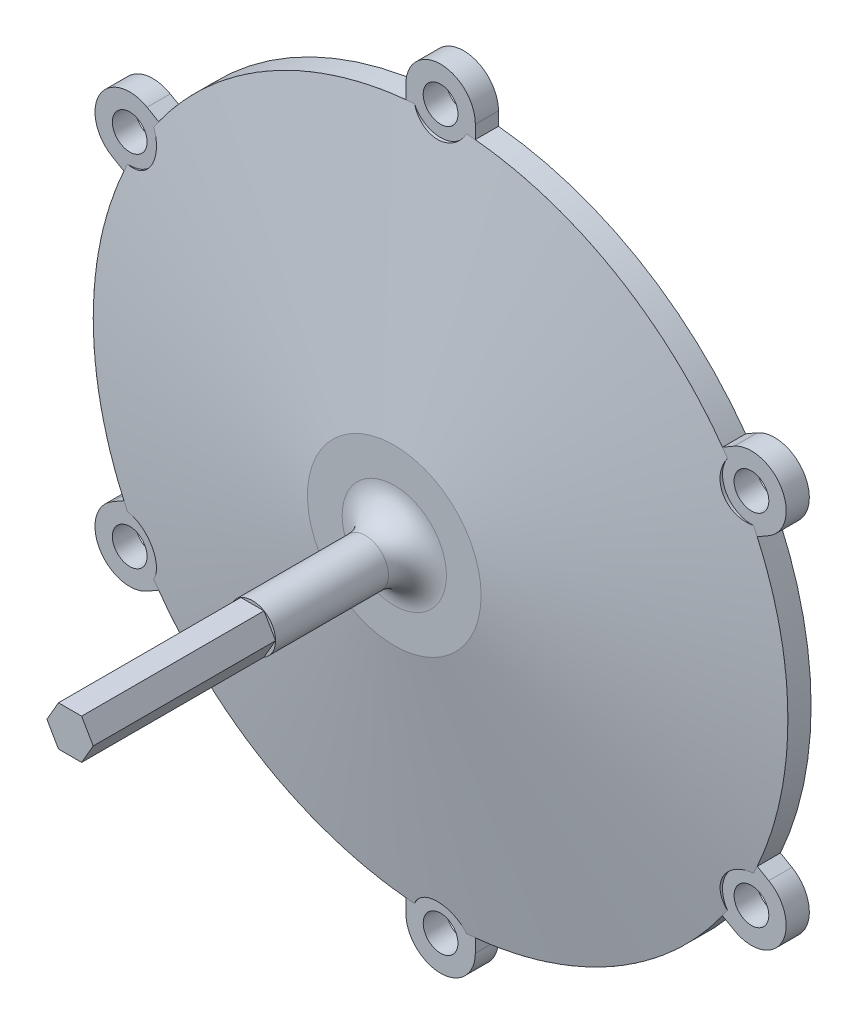
SolidWorks part; units mm, degrees
other "Markup1"
sketch "Sketch15" plane through (-60, 68, 48) normal (-0.9801, 0.1341, 0.1467) x (0.1373, -0.0767, 0.9876)
material "PETG"
ref_plane "Front Plane" through (0, 0, 0) normal (0, 0, 1) x (1, 0, 0)
ref_plane "Top Plane" through (0, 0, 0) normal (0, 1, 0) x (1, 0, 0)
ref_plane "Right Plane" through (0, 0, 0) normal (1, 0, 0) x (0, 0, -1)
sketch "Sketch1" plane through (0, 0, 0) normal (0, 0, 1) x (1, 0, 0)
  line L0 (-6, 62) -> (-6, 59.6992)
  line L1 (6, 62) -> (6, 59.6992)
  line L2 (50.6936, 36.1962) -> (48.7011, 35.0458)
  line L3 (56.6936, 25.8038) -> (54.7011, 24.6535)
  line L4 (56.6936, -25.8038) -> (54.7011, -24.6535)
  line L5 (50.6936, -36.1962) -> (48.7011, -35.0458)
  line L6 (6, -62) -> (6, -59.6992)
  line L7 (-6, -62) -> (-6, -59.6992)
  line L8 (-50.6936, -36.1962) -> (-48.7011, -35.0458)
  line L9 (-56.6936, -25.8038) -> (-54.7011, -24.6535)
  line L10 (-56.6936, 25.8038) -> (-54.7011, 24.6535)
  line L11 (-50.6936, 36.1962) -> (-48.7011, 35.0458)
  line L12 (0, 0) -> (6, 59.6992) construction
  circle A0 centre (0, 0) radius 57
  circle A1 centre (0, 0) radius 60
  arc A2 (6, 62) -> (-6, 62) centre (0, 62) ccw
  arc A3 (56.6936, 25.8038) -> (50.6936, 36.1962) centre (53.6936, 31) ccw
  arc A4 (50.6936, -36.1962) -> (56.6936, -25.8038) centre (53.6936, -31) ccw
  arc A5 (-6, -62) -> (6, -62) centre (0, -62) ccw
  arc A6 (-56.6936, -25.8038) -> (-50.6936, -36.1962) centre (-53.6936, -31) ccw
  arc A7 (-50.6936, 36.1962) -> (-56.6936, 25.8038) centre (-53.6936, 31) ccw
  dimension "D1" = 120
  dimension "D2" = 3
  dimension "D3" = 6
  dimension "D4" = 62
  dimension "D5" = 6
extrude "Boss-Extrude1" add sketch "Sketch1" along normal blind 4 contours L11 A7 L10 A1 | L1 A2 L0 A1 | L3 A3 L2 A1 | L5 A4 L4 A1 | L7 A5 L6 A1 | L9 A6 L8 A1 | A0 A1 region at (0, 63.4372, 0) region at (0, 58.3029, 0) region at (-54.9382, 31.7186, 0) region at (54.9382, 31.7186, 0) region at (-54.9382, -31.7186, 0) region at (54.9382, -31.7186, 0) region at (0, -63.4372, 0)
sketch "Sketch3" plane through (0, 0, 0) normal (0, 1, 0) x (1, 0, 0)
  line L0 (0, -4) -> (60, -4)
  line L1 (-6, -4) -> (6, -4) construction
  line L2 (60, -4) -> (15, -12)
  line L3 (15, -12) -> (0, -12)
  line L4 (0, -12) -> (0, -4)
  line L5 (48.7011, 0) -> (6, 0) construction
  line L6 (48.7011, 0) -> (6, 0) construction
  line L7 (0, -4) -> (60, -4)
  line L8 (0, -4) -> (0, -0.5)
  line L9 (0, -0.5) -> (57, -0.5)
  line L13 (57, -0.5) -> (57, -4)
  line L15 (-57, -4) -> (57, -4) construction
  dimension "D1" = 12
  dimension "D2" = 15
  dimension "D3" = 0.5
  dimension "D4" = 3
revolve "Revolve1" add sketch "Sketch3" angle 360 about L4 region at (28.5, 0, 2.25) region at (21, 0, 7.2)
sketch "Sketch4" plane through (0, 0, 0.5) normal (0, 0, 1) x (1, 0, 0)
  circle A0 centre (0, 0) radius 14
  dimension "D1" = 28
extrude "Cut-Extrude1" cut sketch "Sketch4" along normal blind 7 contours A0
sketch "Sketch9" plane through (0, 0, 7.5) normal (0, 0, -1) x (-1, 0, 0)
  circle A0 centre (0, 0) radius 11.5
  dimension "D1" = 23
extrude "Cut-Extrude4" cut sketch "Sketch9" against normal blind 0.5
sketch "Sketch10" plane through (0, 0, 12) normal (0, 0, 1) x (1, 0, 0)
  circle A0 centre (0, 0) radius 4
  dimension "D1" = 8
extrude "Boss-Extrude2" add sketch "Sketch10" along normal blind 56
fillet "Fillet1" radius 5 1 edges at (4, 0, 12)
sketch "Sketch7" plane through (0, 0, 4) normal (0, 0, 1) x (1, 0, 0)
  circle A0 centre (0, 62) radius 3
  arc A1 (6, 62) -> (-6, 62) centre (0, 62) ccw construction
  dimension "D1" = 6
extrude "Cut-Extrude2" cut sketch "Sketch7" against normal through all
sketch "Sketch8" plane through (0, 0, 4) normal (0, 0, 1) x (1, 0, 0)
  circle A0 centre (0, 62) radius 5
  dimension "D1" = 10
extrude "Cut-Extrude3" cut sketch "Sketch8" along normal through all
pattern_circular "CirPattern6" count 6 over 360 about axis through (0, 0, 4) along (0, 0, 1) of "Cut-Extrude2", "Cut-Extrude3"
sketch "Sketch11" plane through (0, 0, 68) normal (0, 0, 1) x (1, 0, 0)
  line L5 (2, 3.4641) -> (-2, 3.4641)
  line L6 (-2, 3.4641) -> (-4, 0)
  line L7 (-4, 0) -> (-2, -3.4641)
  line L8 (-2, -3.4641) -> (2, -3.4641)
  line L9 (2, -3.4641) -> (4, 0)
  line L10 (4, 0) -> (2, 3.4641)
  circle A1 centre (0, 0) radius 3.4641 construction
  circle A2 centre (0, 0) radius 4 construction
  circle A3 centre (0, 0) radius 4
  circle M5 centre (0, 0) radius 4
extrude "Cut-Extrude5" cut sketch "Sketch11" against normal blind 31.5 contours L6 M5 | L5 M5 | L10 M5 | L9 M5 | L8 M5 | L7 M5 region at (3.1867, 1.8399, 68) region at (0, 3.6797, 68) region at (-3.1867, 1.8399, 68) region at (3.1867, -1.8399, 68) region at (-3.1867, -1.8399, 68) region at (0, -3.6797, 68)
